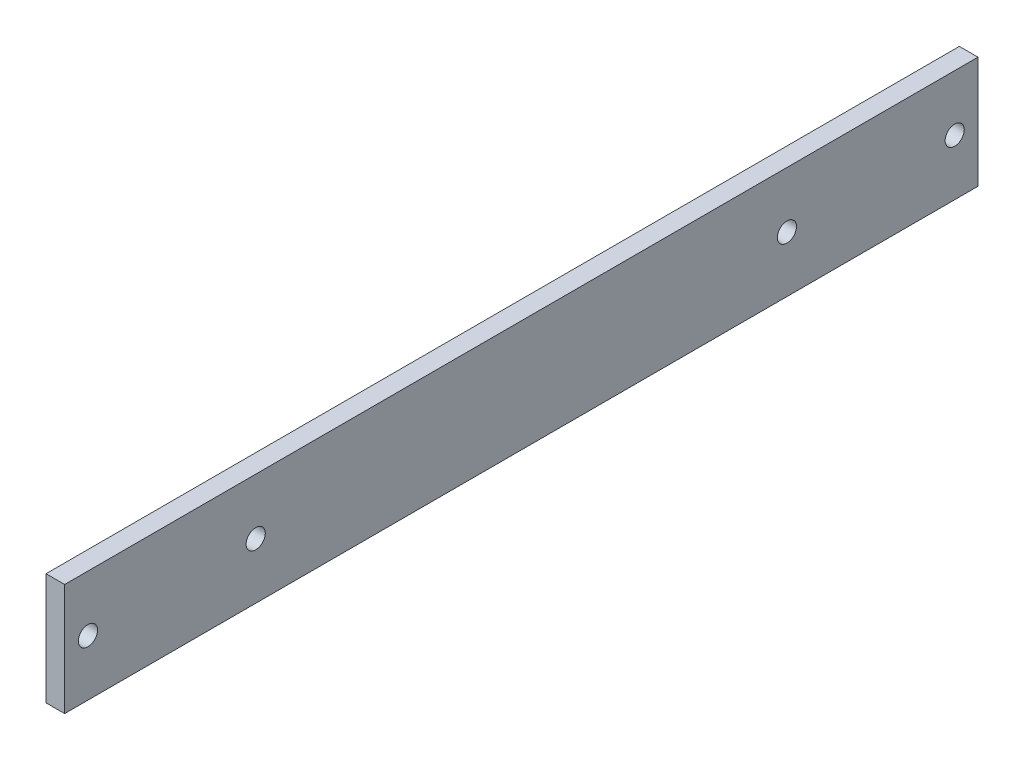
SolidWorks part; units mm, degrees
material "6061-T6 (SS)"
ref_plane "Front" through (0, 0, 0) normal (0, 0, 1) x (1, 0, 0)
ref_plane "Top" through (0, 0, 0) normal (0, 1, 0) x (1, 0, 0)
ref_plane "Right" through (0, 0, 0) normal (1, 0, 0) x (0, 0, -1)
sketch "Sketch1" plane through (0, 0, 0) normal (0, 0, 1) x (1, 0, 0)
  line L1 (-3.175, -19.05) -> (3.175, -19.05)
  line L2 (-3.175, -19.05) -> (-3.175, 19.05)
  line L3 (-3.175, 19.05) -> (3.175, 19.05)
  line L4 (3.175, -19.05) -> (3.175, 19.05)
  line L5 (-3.175, -19.05) -> (3.175, 19.05) construction
  line L6 (-3.175, 19.05) -> (3.175, -19.05) construction
  point P0 (0, 0)
  dimension "D1" = 38.1
  dimension "D2" = 6.35
extrude "Boss-Extrude1" add sketch "Sketch1" along normal mid plane 311.15
sketch "Sketch2" plane through (3.175, 0, 0) normal (1, 0, 0) x (0, 0, -1)
  line L0 (155.575, 0) -> (147.6375, 0) construction
  line L1 (155.575, -19.05) -> (155.575, 19.05) construction
  line L2 (147.6375, 0) -> (90.4875, 0) construction
  line L3 (90.4875, 0) -> (-90.4875, 0) construction
  line L4 (-90.4875, 0) -> (-147.6375, 0) construction
  line L5 (-147.6375, 0) -> (-155.575, 0) construction
  line L6 (-155.575, -19.05) -> (-155.575, 19.05) construction
  point P5 (-119.0625, 0)
  point P12 (119.0625, 0)
  dimension "D1" = 57.15
  dimension "D2" = 238.125
hole_wizard "1/4 Clearance Hole1" positions "Sketch4" profile "Sketch3" hole size "1/4" standard "ANSI Inch"
sketch "Sketch4" plane through (3.175, 0, 0) normal (1, 0, 0) x (0, 0, -1)
  point P0 (-147.6375, 0)
  point P3 (-90.4875, 0)
  point P6 (90.4875, 0)
  point P9 (147.6375, 0)
sketch "Sketch3" plane through (3.175, 0, 147.6375) normal (0, 1, 0) x (0, 0, -1)
  line L0 (0, 0) -> (0, 84.5111)
  line L1 (0, 84.5111) -> (3.2639, 82.55)
  line L2 (3.2639, 82.55) -> (3.2639, 0)
  line L5 (3.2639, 0) -> (0, 0)
  line L10 (0, 84.5111) -> (-3.2639, 82.55) construction
  line L11 (0, -6.35) -> (0, 107.95) construction
  dimension "Hole Dia." = 6.5278
  dimension "Hole Depth" = 82.55
  dimension "Drill Angle" = 118
